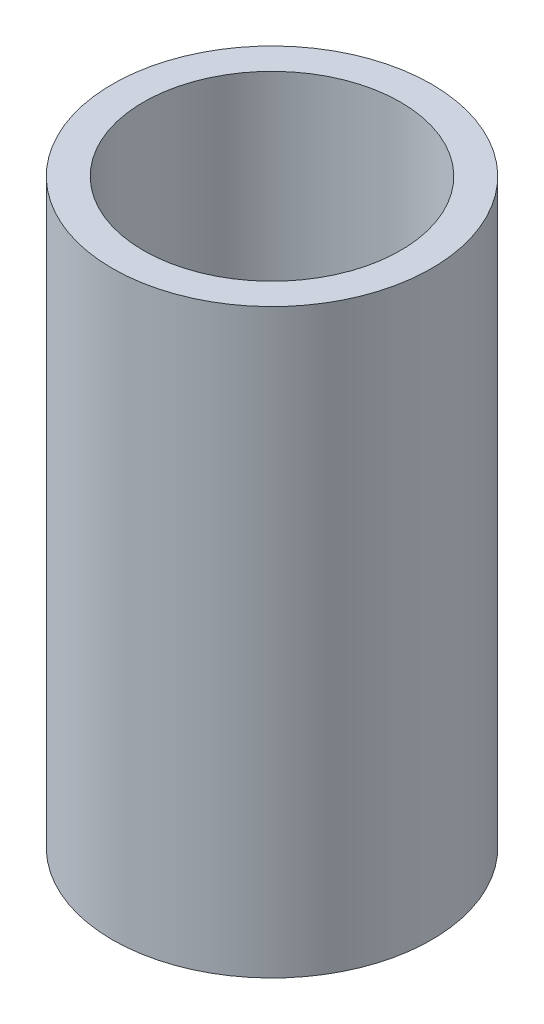
SolidWorks part; units mm, degrees
ref_plane "Front Plane" through (0, 0, 0) normal (0, 0, 1) x (1, 0, 0)
ref_plane "Top Plane" through (0, 0, 0) normal (0, 1, 0) x (1, 0, 0)
ref_plane "Right Plane" through (0, 0, 0) normal (1, 0, 0) x (0, 0, -1)
sketch "Sketch1" plane through (0, 0, 0) normal (0, 1, 0) x (1, 0, 0)
  circle A0 centre (0, 0) radius 22.5
  dimension "SLEEVE_OD" = 45
extrude "Boss-Extrude1" add sketch "Sketch1" along normal blind 81.97
sketch "Sketch2" plane through (0, 0, 0) normal (0, 1, 0) x (1, 0, 0)
  circle A0 centre (0, 0) radius 18.1239
  dimension "BORE_D" = 36.2478
extrude "Cut-Extrude1" cut sketch "Sketch2" along normal through all
chamfer "Chamfer1" distance 2.9125 angle 60 rebuild error yes
